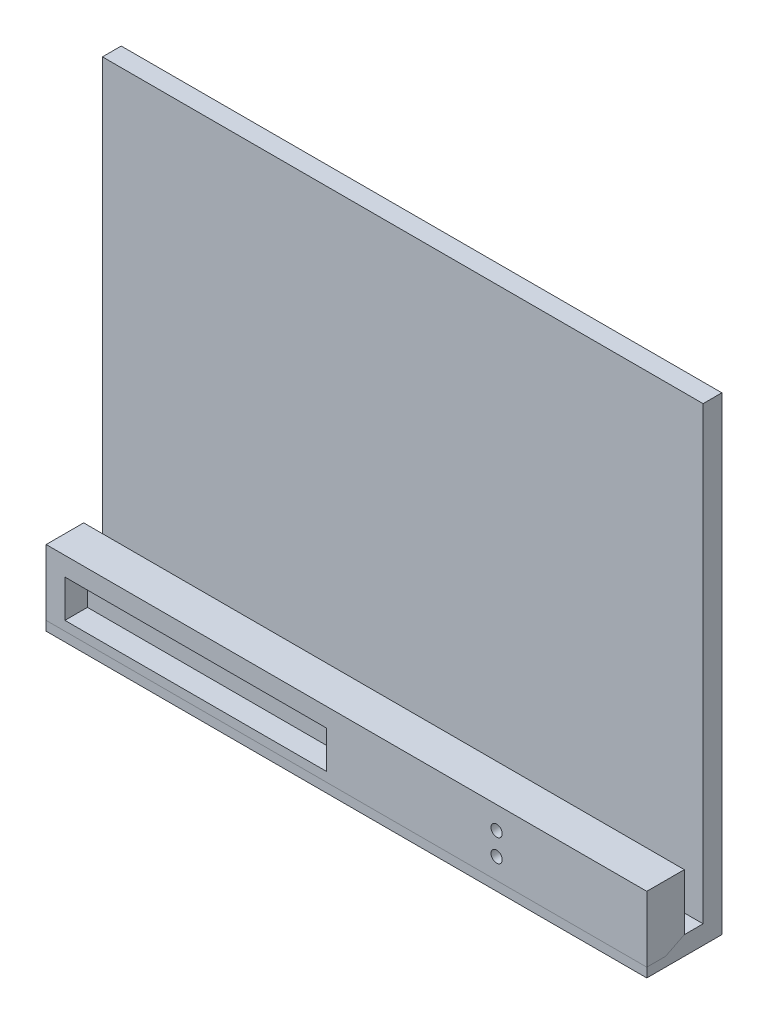
SolidWorks part; units mm, degrees
ref_plane "Front Plane" through (0, 0, 0) normal (0, 0, 1) x (1, 0, 0)
ref_plane "Top Plane" through (0, 0, 0) normal (0, 1, 0) x (1, 0, 0)
ref_plane "Right Plane" through (0, 0, 0) normal (1, 0, 0) x (0, 0, -1)
sketch "Sketch1" plane through (0, 0, 0) normal (0, 0, 1) x (1, 0, 0)
  line L1 (0, 158.75) -> (203.2, 158.75)
  line L2 (0, 158.75) -> (0, 0)
  line L3 (0, 0) -> (203.2, 0)
  line L4 (203.2, 158.75) -> (203.2, 0)
  dimension "D1" = 158.75
  dimension "D2" = 203.2
extrude "Boss-Extrude1" add sketch "Sketch1" along normal blind 6.35
sketch "Sketch2" plane through (0, 0, 6.35) normal (0, 0, 1) x (1, 0, 0)
  line L0 (0, 158.75) -> (0, 0) construction
  line L1 (0, 6.35) -> (203.2, 6.35)
  line L2 (0, 6.35) -> (0, 0)
  line L3 (0, 0) -> (203.2, 0)
  line L4 (203.2, 6.35) -> (203.2, 0)
  dimension "D1" = 6.35
extrude "Boss-Extrude2" add sketch "Sketch2" along normal blind 19.05
sketch "Sketch3" plane through (0, 6.35, 0) normal (0, 1, 0) x (1, 0, 0)
  line L6 (203.2, -25.4) -> (203.2, -6.35) construction
  line L7 (0, -25.4) -> (203.2, -25.4)
  line L8 (0, -25.4) -> (0, -12.7)
  line L9 (0, -12.7) -> (203.2, -12.7)
  line L10 (203.2, -25.4) -> (203.2, -12.7)
  dimension "D1" = 12.7
extrude "Boss-Extrude3" add sketch "Sketch3" along normal blind 19.05
sketch "Sketch4" plane through (0, 0, 25.4) normal (0, 0, 1) x (1, 0, 0)
  line L0 (0, 25.4) -> (0, 0) construction
  line L1 (6.35, 19.05) -> (94.9058, 19.05)
  line L2 (6.35, 19.05) -> (6.35, 6.35)
  line L3 (6.35, 6.35) -> (94.9058, 6.35)
  line L4 (94.9058, 19.05) -> (94.9058, 6.35)
  line L5 (0, 25.4) -> (203.2, 25.4) construction
  dimension "D1" = 6.35
  dimension "D2" = 12.7
  dimension "D3" = 6.35
extrude "Cut-Extrude1" cut sketch "Sketch4" against normal blind 7.62
sketch "Sketch5" plane through (0, 0, 25.4) normal (0, 0, 1) x (1, 0, 0)
  line L0 (152.4, 25.4) -> (152.4, 0) construction
  line L1 (0, 25.4) -> (203.2, 25.4) construction
  line L2 (0, 0) -> (203.2, 0) construction
  line L3 (203.2, 0) -> (203.2, 25.4) construction
  circle A0 centre (152.4, 17.78) radius 1.905
  circle A1 centre (152.4, 10.16) radius 1.905
  dimension "D1" = 3.81
  dimension "D2" = 3.81
  dimension "D3" = 50.8
  dimension "D4" = 10.16
  dimension "D5" = 7.62
extrude "Cut-Extrude2" cut sketch "Sketch5" against normal up to next
sketch "Sketch6" plane through (203.2, 0, 0) normal (1, 0, 0) x (0, 0, -1)
  line L0 (-25.4, 3.175) -> (-19.05, 3.175)
  line L1 (-25.4, 0) -> (-25.4, 25.4) construction
  line L2 (-19.05, 3.175) -> (-12.7, 6.35)
  line L3 (-25.4, 0) -> (0, 0) construction
  dimension "D1" = 6.35
  dimension "D2" = 3.175
split "Split1" trim tools "Sketch6" bodies to split 105 resulting bodies 111 112
